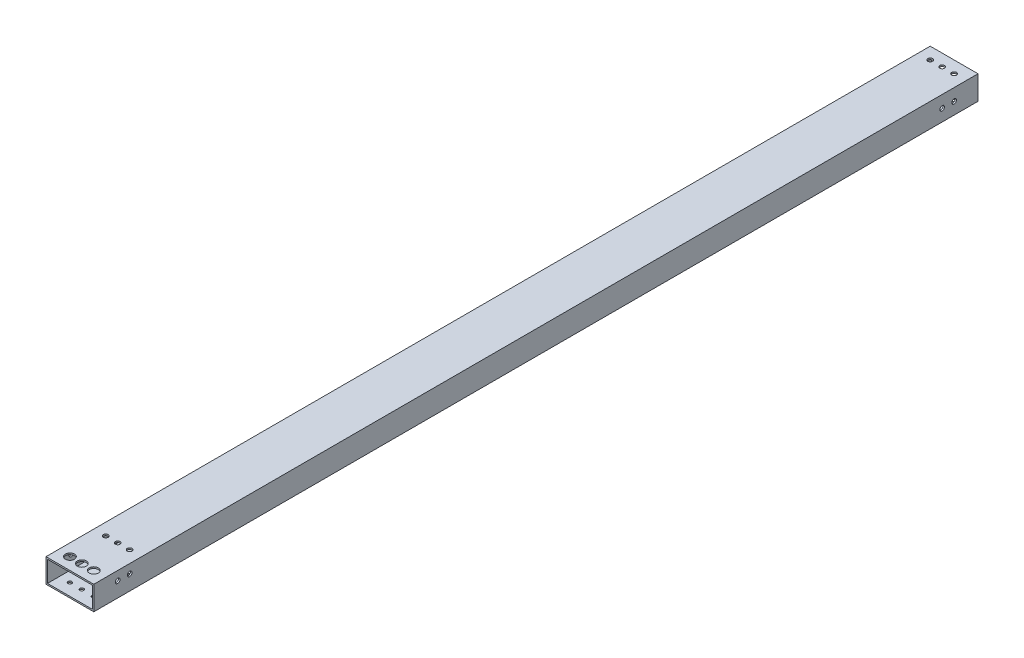
SolidWorks part; units mm, degrees
material "6061-T6 (SS)"
ref_plane "Front Plane" through (0, 0, 0) normal (0, 0, 1) x (1, 0, 0)
ref_plane "Top Plane" through (0, 0, 0) normal (0, 1, 0) x (1, 0, 0)
ref_plane "Right Plane" through (0, 0, 0) normal (1, 0, 0) x (0, 0, -1)
sketch "Sketch1" plane through (0, 0, 0) normal (0, 0, 1) x (1, 0, 0)
  line L0 (-23.8125, 11.1125) -> (23.8125, 11.1125)
  line L1 (-25.4, -12.7) -> (25.4, -12.7)
  line L2 (-25.4, -12.7) -> (-25.4, 12.7)
  line L3 (-25.4, 12.7) -> (25.4, 12.7)
  line L4 (25.4, -12.7) -> (25.4, 12.7)
  line L5 (-25.4, -12.7) -> (25.4, 12.7) construction
  line L6 (-25.4, 12.7) -> (25.4, -12.7) construction
  line L7 (23.8125, -11.1125) -> (23.8125, 11.1125)
  line L8 (-23.8125, -11.1125) -> (23.8125, -11.1125)
  line L9 (-23.8125, -11.1125) -> (-23.8125, 11.1125)
  point P0 (0, 0)
  dimension "D1" = 50.8
  dimension "D2" = 25.4
  dimension "D3" = 1.5875
extrude "Boss-Extrude1" add sketch "Sketch1" along normal mid plane 939.8
sketch "Sketch4" plane through (0, 12.7, 0) normal (0, 1, 0) x (1, 0, 0)
  line L0 (25.4, -469.9) -> (-25.4, -469.9) construction
  circle A0 centre (-12.7, -457.2) radius 4.826
  circle A1 centre (0, -457.2) radius 4.826
  circle A2 centre (12.7, -457.2) radius 4.826
  dimension "D1" = 9.652
  dimension "D2" = 12.7
  dimension "D3" = 12.7
  dimension "D4" = 12.7
extrude "Cut-Extrude3" cut sketch "Sketch4" against normal up to surface (1.5875 mm away) contours A0 | A1 | A2 region at (-12.7, 12.7, 457.2) region at (0, 12.7, 457.2) region at (12.7, 12.7, 457.2) up to face at (0, 11.1125, 0)
sketch "Sketch5" plane through (0, -12.7, 0) normal (0, -1, 0) x (1, 0, 0)
  circle A0 centre (-12.7, 457.2) radius 4.826 construction
  circle A1 centre (0, 457.2) radius 4.826 construction
  circle A2 centre (12.7, 457.2) radius 4.826 construction
  circle A3 centre (-12.7, 457.2) radius 4.826
  circle A4 centre (0, 457.2) radius 4.826
  circle A5 centre (12.7, 457.2) radius 4.826
  circle A6 centre (-12.7, 457.2) radius 2.0193
  circle A7 centre (0, 457.2) radius 2.0193
  circle A8 centre (12.7, 457.2) radius 2.0193
  dimension "D1" = 4.0386
  dimension "D2" = 4.0386
  dimension "D3" = 4.0386
extrude "Cut-Extrude4" cut sketch "Sketch5" against normal up to surface (1.5875 mm away) contours A8 | A7 | A6 region at (-12.7, -12.7, 457.2) region at (0, -12.7, 457.2) region at (12.7, -12.7, 457.2) up to face at (0, -11.1125, 0)
sketch "Sketch6" plane through (0, -12.7, 0) normal (0, -1, 0) x (1, 0, 0)
  line L0 (-25.4, -469.9) -> (25.4, -469.9) construction
  circle A0 centre (-12.7, -457.2) radius 2.5527
  circle A1 centre (0, -457.2) radius 2.5527
  circle A2 centre (12.7, -457.2) radius 2.5527
  dimension "D1" = 5.1054
  dimension "D2" = 12.7
  dimension "D3" = 12.7
  dimension "D4" = 12.7
extrude "Cut-Extrude5" cut sketch "Sketch6" against normal through all contours A2 | A1 | A0 region at (-12.7, -12.7, -457.2) region at (0, -12.7, -457.2) region at (12.7, -12.7, -457.2)
sketch "Sketch7" plane through (25.4, 0, 0) normal (1, 0, 0) x (0, 0, -1)
  line L0 (-469.9, -12.7) -> (-469.9, 12.7) construction
  line L2 (469.9, -12.7) -> (469.9, 12.7) construction
  line L3 (-469.9, -12.7) -> (469.9, -12.7) construction
  circle A0 centre (-457.2, 3.175) radius 2.4892
  circle A1 centre (-444.5, 3.175) radius 2.4892
  circle A2 centre (-431.8, 3.175) radius 2.4892
  circle A3 centre (-419.1, 3.175) radius 2.4892
  circle A4 centre (457.2, 0) radius 2.4892
  circle A5 centre (444.5, 0) radius 2.4892
  circle A6 centre (431.8, 0) radius 2.4892
  dimension "D1" = 4.9784
  dimension "D7" = 4.9784
  dimension "D8" = 12.7
  dimension "D2" = 12.7
  dimension "D3" = 12.7
  dimension "D4" = 12.7
  dimension "D5" = 12.7
  dimension "D6" = 15.875
  dimension "D9" = 12.7
  dimension "D10" = 12.7
  dimension "D11" = 12.7
extrude "Cut-Extrude6" cut sketch "Sketch7" against normal through all contours A6 | A5 | A1 | A2 region at (25.4, 3.175, 444.5) region at (25.4, 3.175, 431.8) region at (25.4, 0, -444.5) region at (25.4, 0, -431.8)
sketch "Sketch9" plane through (0, 12.7, 0) normal (0, 1, 0) x (1, 0, 0)
  line L0 (25.4, -469.9) -> (-25.4, -469.9) construction
  circle A0 centre (-12.7, -419.1) radius 2.5527
  circle A1 centre (0, -419.1) radius 2.5527
  circle A2 centre (12.7, -419.1) radius 2.5527
  point P6 (0, 0)
  point P8 (0, 0)
  point P11 (0, 0)
  dimension "D1" = 5.1054
  dimension "D2" = 12.7
  dimension "D3" = 12.7
  dimension "D4" = 50.8
extrude "Cut-Extrude7" cut sketch "Sketch9" against normal through all
